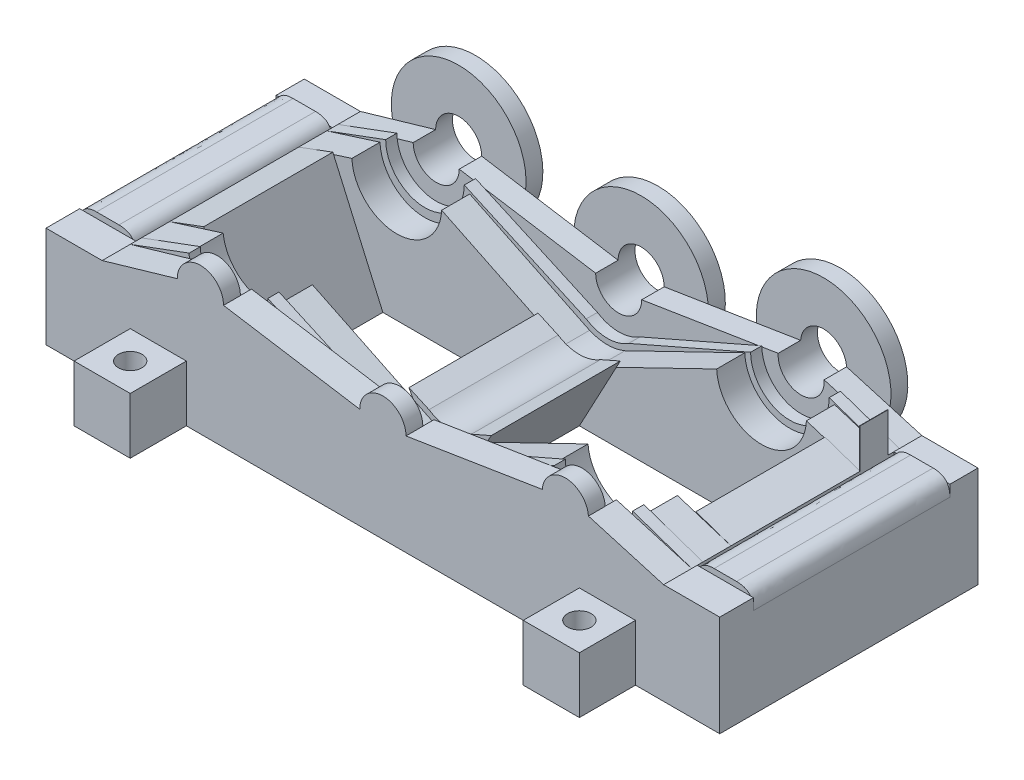
SolidWorks part; units mm, degrees
ref_plane "Спереди" through (0, 0, 0) normal (0, 0, 1) x (1, 0, 0)
ref_plane "Сверху" through (0, 0, 0) normal (0, 1, 0) x (1, 0, 0)
ref_plane "Справа" through (0, 0, 0) normal (1, 0, 0) x (0, 0, -1)
sketch "Эскиз1" plane through (0, 0, 0) normal (0, 1, 0) x (1, 0, 0)
  line L4 (-60, 16) -> (-60, 11)
  line L5 (-60, -30) -> (-60, -24)
  line L6 (-60, -24) -> (-60, 11)
  line L7 (60, 16) -> (60, 11)
  line L8 (60, 11) -> (60, -24)
  line L9 (60, -24) -> (60, -30)
  line L10 (-60, 11) -> (-50, 11)
  line L11 (-60, -24) -> (-50, -24)
  line L12 (-60, 16) -> (-55, 16)
  line L13 (-55, 16) -> (55, 16)
  line L14 (55, 16) -> (60, 16)
  line L15 (-60, 16) -> (-60, 43)
  line L16 (-60, 43) -> (-60, 48)
  line L17 (-60, -30) -> (-45, -30)
  line L18 (-45, -30) -> (-35, -30)
  line L19 (-35, -30) -> (35, -30)
  line L20 (35, -30) -> (45, -30)
  line L21 (45, -30) -> (60, -30)
  line L22 (-60, -45) -> (-60, -30)
  line L23 (-60, -45) -> (-45, -45)
  line L24 (-45, -40) -> (-35, -40)
  line L25 (-35, -40) -> (-35, -30)
  line L26 (-45, -30) -> (-45, -40)
  line L27 (-45, -45) -> (-45, -40)
  line L28 (60, -30) -> (60, -45)
  line L29 (35, -40) -> (45, -40)
  line L30 (45, -45) -> (45, -40)
  line L31 (45, -40) -> (45, -30)
  line L32 (35, -30) -> (35, -40)
  line L33 (45, -45) -> (60, -45)
  line L34 (-50, -24) -> (50, -24)
  line L35 (50, -24) -> (60, -24)
  line L36 (-50, 11) -> (50, 11)
  line L37 (50, 11) -> (60, 11)
  line L38 (-50, -24) -> (-50, 11)
  line L39 (50, -24) -> (50, 11)
  line L40 (60, 16) -> (60, 43)
  line L41 (60, 43) -> (60, 48)
  line L42 (55, 16) -> (55, 43)
  line L43 (55, 43) -> (-55, 43)
  line L44 (-55, 43) -> (-55, 16)
  line L45 (-60, 48) -> (-45, 48)
  line L46 (-45, 48) -> (-35, 48)
  line L47 (60, 48) -> (45, 48)
  line L48 (45, 48) -> (35, 48)
  line L49 (35, 48) -> (-35, 48)
  line L50 (-60, 63) -> (-60, 48)
  line L51 (-60, 63) -> (-45, 63)
  line L52 (-45, 58) -> (-45, 48)
  line L53 (-45, 58) -> (-45, 63)
  line L54 (-45, 58) -> (-35, 58)
  line L55 (-35, 58) -> (-35, 48)
  line L56 (60, 48) -> (60, 63)
  line L57 (60, 63) -> (45, 63)
  line L58 (45, 63) -> (45, 58)
  line L59 (45, 58) -> (45, 48)
  line L60 (45, 58) -> (35, 58)
  line L61 (35, 58) -> (35, 48)
  circle A0 centre (-40, -35) radius 2.1
  circle A1 centre (-52.5, -37.5) radius 3
  circle A2 centre (40, -35) radius 2.1
  circle A3 centre (52.5, -37.5) radius 3
  circle A4 centre (-52.5, 55.5) radius 3
  circle A5 centre (-40, 53) radius 2.1
  circle A6 centre (40, 53) radius 2.1
  circle A7 centre (52.5, 55.5) radius 3
extrude "Бобышка-Вытянуть4" add sketch "Эскиз1<5>" along normal blind 10 contours L18 L26 L24 L25 A0 | L20 L32 L29 L31 A2 region at (-40, 0, 30.1414) region at (40, 0, 30.1414)
sketch "Эскиз1<5>" plane through (0, 0, 0) normal (0, 1, 0) x (1, 0, 0) same geometry as "Эскиз1"
extrude "Бобышка-Вытянуть5" add sketch "Эскиз1<6>" along normal blind 35 contours L48 L49 L46 L45 L16 L15 L12 L44 L43 L42 L14 L40 L41 L47 | L55 L54 L52 L46 A5 | L60 L61 L48 L59 A6 region at (-58.7581, 0, -29.5) region at (-44.8586, 0, -53) region at (35.1414, 0, -53)
sketch "Эскиз1<6>" plane through (0, 0, 0) normal (0, 1, 0) x (1, 0, 0) same geometry as "Эскиз1"
extrude "Бобышка-Вытянуть7" add sketch "Эскиз1" along normal blind 19 contours L39 L35 L8 L37 | L11 L38 L10 L6 region at (-55, 0, 6.5) region at (55, 0, 6.5)
fillet "Скругление8" radius 3 2 edges at (-60, 19, 6.5) (-50, 19, 6.5) conic rho 0.5
fillet "Скругление9" radius 3 2 edges at (50, 19, 6.5) (60, 19, 6.5) conic rho 0.5
extrude "Бобышка-Вытянуть8" add sketch "Эскиз1<9>" along normal blind 18 contours L36 L37 L7 L14 L13 L12 L4 L10 | L35 L34 L11 L5 L17 L18 L19 L20 L21 L9 region at (0, 0, -13.5) region at (0, 0, 27)
sketch "Эскиз1<9>" plane through (0, 0, 0) normal (0, 1, 0) x (1, 0, 0) same geometry as "Эскиз1"
ref_plane "Плоскость1" through (-60, 0, 0) normal (-1, 0, 0) x (0, 0, 1)
sketch "Эскиз2" plane through (-60, 0, 0) normal (-1, 0, 0) x (0, 0, 1)
  line L0 (-58, 0) -> (-21, 0)
  line L7 (30, 0) -> (-48, 0) construction
  line L8 (-21, 0) -> (-21, 30)
  line L9 (-21, 30) -> (-58, 30)
  line L10 (-58, 30) -> (-58, 0)
extrude "Вырез-Вытянуть2" cut sketch "Эскиз2" against normal through all
ref_plane "Плоскость2" through (0, 0, 30) normal (0, 0, 1) x (1, 0, 0)
sketch "Эскиз3" plane through (0, 0, 30) normal (0, 0, 1) x (1, 0, 0)
  line L0 (-4.1, 18) -> (4.1, 18)
  arc A1 (-4.1, 18) -> (4.1, 18) centre (0, 18) ccw
extrude "Вырез-Вытянуть3" cut sketch "Эскиз3" against normal through all both and the other way through all
ref_plane "Плоскость3" through (0, 0, -16) normal (0, 0, -1) x (-1, 0, 0)
sketch "Эскиз6" plane through (0, 0, -16) normal (0, 0, -1) x (-1, 0, 0)
  line L13 (31.2351, 18) -> (33.7649, 18)
  line L18 (-28.4105, 21.9) -> (-4.1, 18)
  line L20 (-50, 18) -> (-34.4499, 18)
  line L22 (28.4, 21.9) -> (36.6, 21.9)
  line L23 (36.6, 21.9) -> (50, 18)
  line L24 (28.4, 21.9) -> (4.1, 18)
  line L25 (4.1, 18) -> (31.2351, 18)
  line L26 (50, 18) -> (33.7649, 18)
  line L28 (-30.5501, 18) -> (-4.1, 18)
  line L29 (-36.5895, 21.9) -> (-50, 18)
  line L31 (-34.4499, 18) -> (-30.5501, 18)
  arc A6 (28.4, 21.9) -> (31.2351, 18) centre (32.5, 21.9) ccw
  arc A12 (31.2351, 18) -> (33.7649, 18) centre (32.5, 21.9) ccw
  arc A13 (33.7649, 18) -> (36.6, 21.9) centre (32.5, 21.9) ccw
  arc A16 (-30.5501, 18) -> (-28.4105, 21.9) centre (-32.5, 21.6066) ccw
  arc A20 (-36.5895, 21.9) -> (-34.4499, 18) centre (-32.5, 21.6066) ccw
  arc A21 (-34.4499, 18) -> (-30.5501, 18) centre (-32.5, 21.6066) ccw
ref_plane "Плоскость4" through (0, 0, 30) normal (0, 0, 1) x (1, 0, 0)
sketch "Эскиз9" plane through (-60, 0, 0) normal (-1, 0, 0) x (0, 0, 1)
  line L0 (-58, 34.892) -> (-58, 35)
  line L1 (-58, 35) -> (-58, 30) construction
  line L2 (-58, 34.9) -> (-58, 43.9) construction
  line L3 (-58, 35) -> (-16, 35)
  line L4 (-16, 35) -> (-16, 34.9)
  line L5 (-16, 35) -> (-16, 18) construction
  line L6 (-16, 34.9) -> (-16, 44.9) construction
  line L7 (-16, 34.9) -> (-58, 34.892)
extrude "Вырез-Вытянуть6" cut sketch "Эскиз9" against normal through all both and the other way through all
ref_plane "Плоскость5" through (0, 0, 24) normal (0, 0, -1) x (-1, 0, 0)
ref_plane "Плоскость6" through (0, 0, -16) normal (0, 0, -1) x (-1, 0, 0)
sketch "Эскиз13" plane through (0, 0, -16) normal (0, 0, -1) x (-1, 0, 0)
  circle A0 centre (0, 18) radius 4.1
  circle A1 centre (0, 18) radius 12
  circle A2 centre (-32.5, 21.6066) radius 4.1
  circle A3 centre (-32.5, 21.6066) radius 12
  circle A4 centre (32.5, 21.9) radius 4.1
  circle A5 centre (32.5, 21.9) radius 12
extrude "Бобышка-Вытянуть20" add sketch "Эскиз13" along normal blind 3
ref_plane "Плоскость7" through (0, 0, 0) normal (0, -1, 0) x (-1, 0, 0)
sketch "Эскиз14" plane through (0, 0, 0) normal (0, -1, 0) x (-1, 0, 0)
  line L0 (-55, 16) -> (-55, 43)
  line L1 (-55, 43) -> (55, 43)
  line L2 (-55, 43) -> (55, 43) construction
  line L3 (55, 43) -> (55, 16)
  line L4 (55, 16) -> (60, 16)
  line L5 (60, -30) -> (60, 21) construction
  line L6 (9.9, 16) -> (-9.9, 16) construction
  line L7 (60, 16) -> (60, 63)
  line L8 (60, 63) -> (-60, 63)
  line L9 (-45, 63) -> (-60, 63) construction
  line L10 (-60, 63) -> (-60, 16)
  line L11 (-60, 21) -> (-60, -30) construction
  line L12 (-60, 16) -> (-55, 16)
  line L13 (-60, 63) -> (-60, 16) construction
extrude "Вырез-Вытянуть9" cut sketch "Эскиз14" against normal blind 40
extrude "Бобышка-Вытянуть21" add sketch "Эскиз6" against normal blind 5 contours A20 L29 L20 | A16 L28 L18 | A6 L24 L25 | A13 L26 L23 region at (-20.8202, 19.2763, -16) region at (-40.5357, 19.259, -16) region at (40.6671, 19.2635, -16) region at (20.6921, 19.2791, -16)
extrude "Вырез-Вытянуть10" cut sketch "Эскиз6<10>" against normal blind 5 contours L31 A21 | L13 A12 region at (-32.5, 17.9198, -16) region at (32.5, 17.8016, -16)
sketch "Эскиз6<10>" plane through (0, 0, -16) normal (0, 0, -1) x (-1, 0, 0) same geometry as "Эскиз6"
sketch "Эскиз15" plane through (0, 0, 30) normal (0, 0, 1) x (1, 0, 0)
  line L0 (-33.7649, 18) -> (-31.2351, 18)
  line L1 (-60, 18) -> (-4.1, 18) construction
  line L2 (-31.2351, 18) -> (-4.1, 18)
  line L3 (-4.1, 18) -> (-28.4, 21.9)
  line L5 (-33.7649, 18) -> (-50, 18)
  line L6 (-36.6, 21.9) -> (-50, 18) construction
  line L7 (-50, 18) -> (-36.6, 21.9)
  line L8 (30.5255, 18) -> (34.4618, 18)
  line L9 (4.1, 18) -> (60, 18) construction
  line L10 (34.4618, 18) -> (50, 18)
  line L11 (36.5895, 21.9) -> (50, 18) construction
  line L15 (4.1, 18) -> (30.5255, 18)
  line L16 (36.5895, 21.9) -> (50, 18)
  line L17 (4.1, 18) -> (28.4105, 21.9)
  arc A2 (-36.6, 21.9) -> (-33.7649, 18) centre (-32.5, 21.9) ccw
  arc A3 (-31.2351, 18) -> (-28.4, 21.9) centre (-32.5, 21.9) ccw
  arc A4 (-31.2351, 18) -> (-33.7649, 18) centre (-32.5, 21.9) cw
  arc A6 (30.5255, 18) -> (34.4618, 18) centre (32.4936, 21.5995) ccw
  arc A8 (28.4105, 21.9) -> (30.5255, 18) centre (32.4869, 21.5871) ccw
  arc A9 (34.4618, 18) -> (36.5895, 21.9) centre (32.49, 21.6061) ccw
extrude "Бобышка-Вытянуть22" add sketch "Эскиз15" against normal blind 6 contours A2 L7 L5 | A3 L2 L3 | A8 L17 L15 | A9 L10 L16 region at (-20.8202, 19.2763, 30) region at (-40.5357, 19.259, 30) region at (40.6688, 19.2637, 30) region at (20.6854, 19.2792, 30)
extrude "Вырез-Вытянуть11" cut sketch "Эскиз15<4>" against normal blind 6 contours A4 L0 | L8 A6 region at (-32.5, 17.9198, 30) region at (32.4936, 17.7977, 30)
sketch "Эскиз15<4>" plane through (0, 0, 30) normal (0, 0, 1) x (1, 0, 0) same geometry as "Эскиз15"
sketch "Эскиз16" plane through (0, 0, 30) normal (0, 0, 1) x (1, 0, 0)
  circle A0 centre (-32.5, 21.9) radius 4.12
  circle A1 centre (0, 18) radius 4.12
  circle A2 centre (32.5, 21.6066) radius 4.12
extrude "Бобышка-Вытянуть45" add sketch "Эскиз16" against normal blind 3
sketch "Эскиз18" plane through (0, 0, 24) normal (0, 0, -1) x (-1, 0, 0)
  line L0 (-50, 18) -> (-50, 0)
  line L1 (-55.3642, 0) -> (55.3642, 0) construction
  line L2 (50, 18) -> (50, 0)
  line L3 (50, 16) -> (50, 0) construction
  line L4 (50, 0) -> (-50, 0)
  line L5 (50, 18) -> (38.9635, 21.2121)
  line L6 (36.6, 21.9) -> (50, 18) construction
  line L7 (26.0113, 21.5166) -> (6.4887, 18.3834)
  line L8 (28.4, 21.9) -> (4.1, 18) construction
  line L9 (-26.0006, 21.5166) -> (-6.4887, 18.3832)
  line L10 (-28.4105, 21.9) -> (-4.1, 18) construction
  line L11 (-50, 18) -> (-38.988, 21.2121)
  arc A3 (-38.988, 21.2121) -> (-26.0006, 21.5166) centre (-32.5, 21.6066) ccw
  arc A4 (6.4887, 18.3834) -> (-6.4887, 18.3832) centre (0, 18) cw
  arc A5 (38.9635, 21.2121) -> (26.0113, 21.5166) centre (32.5, 21.9) cw
extrude "Вырез-Вытянуть12" cut sketch "Эскиз18" along normal blind 36 and the other way blind 1
sketch "Эскиз19" plane through (0, 0, 0) normal (0, -1, 0) x (-1, 0, 0)
  line L0 (-50, -25) -> (-50, -23)
  line L2 (-50, -25) -> (-50, 12) construction
  line L3 (-50, -23) -> (-50, -18)
  line L4 (-50, -18) -> (-50, 5)
  line L5 (-50, 5) -> (-50, 10)
  line L6 (-50, 10) -> (-50, 12)
  line L7 (-50, 12) -> (50, 12)
  line L8 (-50, 10) -> (50, 10)
  line L9 (50, -25) -> (50, 12) construction
  line L10 (-50, 5) -> (50, 5)
  line L11 (-50, -18) -> (50, -18)
  line L12 (-50, -23) -> (50, -23)
  line L13 (-50, -25) -> (50, -25)
  line L14 (50, -25) -> (50, -23)
  line L15 (50, -18) -> (50, 5)
  line L16 (50, 10) -> (50, 12)
  line L17 (50, -18) -> (50, -23)
  line L18 (50, 10) -> (50, 5)
extrude "Бобышка-Вытянуть46" add sketch "Эскиз19" against normal blind 25 contours L18 L8 L5 L10 | L17 L11 L3 L12 region at (0, 0, 20.5) region at (0, 0, -7.5)
ref_plane "Плоскость9" through (0, 0, 23) normal (0, 0, 1) x (1, 0, 0)
sketch "Эскиз21" plane through (0, 0, 23) normal (0, 0, 1) x (1, 0, 0)
  line L0 (-24.5516, 20.9931) -> (-3.2499, 10.6579)
  line L2 (3.1623, 10.6198) -> (24.5344, 20.9749)
  line L3 (40.4673, 20.9971) -> (50, 18)
  line L4 (50, 18) -> (50, 32.9969)
  line L5 (-40.4505, 21.0111) -> (-50, 18)
  line L6 (-50, 18) -> (-50, 32.9969)
  line L7 (-50, 32.9969) -> (50, 32.9969)
  circle A0 centre (0, 18) radius 8.0292
  circle A1 centre (-32.5, 21.9) radius 8
  circle A2 centre (32.5, 21.6066) radius 7.9906
extrude "Вырез-Вытянуть15" cut sketch "Эскиз21" against normal blind 5 contours A2 L3 L4 L7 L6 L5 A1 L0 A0 L2 | L0 A0 L2 | A1 | A2 region at (0.1494, 26.3073, 23) region at (-32.5, 21.9, 23) region at (0, 18.0002, 23) region at (32.5, 21.6066, 23)
ref_plane "Плоскость10" through (0, 0, -5) normal (0, 0, 1) x (1, 0, 0)
sketch "Эскиз22" plane through (0, 0, -5) normal (0, 0, 1) x (1, 0, 0)
  line L0 (-24.5312, 21) -> (-3.182, 10.6466)
  line L2 (3.1197, 10.6466) -> (24.4532, 21)
  line L3 (40.4376, 21) -> (49.9376, 18)
  line L4 (49.9376, 18) -> (49.9376, 32.9969)
  line L5 (-40.5156, 21) -> (-50, 18)
  line L6 (-50, 18) -> (-50, 32.9969)
  line L7 (-50, 32.9969) -> (49.9376, 32.9969)
  circle A0 centre (-0.0312, 18) radius 8
  circle A1 centre (-32.5234, 21.353) radius 8
  circle A2 centre (32.4454, 21.353) radius 8
extrude "Вырез-Вытянуть16" cut sketch "Эскиз22" against normal blind 5 contours A2 L3 L4 L7 L6 L5 A1 L0 A0 L2 | A2 | L0 A0 L2 | A1 region at (-0.03, 26.3324, -5) region at (-32.5234, 21.353, -5) region at (-0.0312, 18.0003, -5) region at (32.4454, 21.353, -5)
extrude "Бобышка-Вытянуть47" add sketch "Эскиз19<4>" against normal blind 25 contours L8 L16 L7 L6 region at (0, 0, -11)
sketch "Эскиз19<4>" plane through (0, 0, 0) normal (0, -1, 0) x (-1, 0, 0) same geometry as "Эскиз19"
ref_plane "Плоскость11" through (0, 0, -10) normal (0, 0, 1) x (1, 0, 0)
sketch "Эскиз23" plane through (0, 0, -10) normal (0, 0, 1) x (1, 0, 0)
  line L0 (-25.5, 21.9) -> (-3.7867, 12.1127)
  line L2 (3.7867, 12.1127) -> (25.5, 21.6066)
  line L3 (39.5, 21.6066) -> (50, 18)
  line L4 (50, 18) -> (50, 33)
  line L5 (-39.5, 21.9) -> (-50, 18)
  line L6 (-50, 18) -> (-50, 33)
  line L7 (-50, 33) -> (50, 33)
  circle A3 centre (0, 18) radius 7
  circle A4 centre (-32.5, 21.9) radius 7
  circle A5 centre (32.5, 21.6066) radius 7
extrude "Вырез-Вытянуть18" cut sketch "Эскиз23" against normal blind 2 contours A5 L3 L4 L7 L6 L5 A4 L0 A3 L2 | A4 | A3 | A5 L0 region at (0.2254, 26.3963, -10) region at (-32.5, 21.9, -10) region at (0, 18, -10) region at (32.5, 21.6066, -10)
extrude "Бобышка-Вытянуть49" add sketch "Эскиз19<6>" against normal blind 25 contours L11 L15 L10 L4 | L13 L14 L12 L0 region at (0, 0, 24) region at (0, 0, 6.5)
sketch "Эскиз19<6>" plane through (0, 0, 0) normal (0, -1, 0) x (-1, 0, 0) same geometry as "Эскиз19"
ref_plane "Плоскость12" through (0, 0, 18) normal (0, 0, 1) x (1, 0, 0)
ref_plane "Плоскость13" through (0, 0, 25) normal (0, 0, 1) x (1, 0, 0)
sketch "Эскиз24" plane through (0, 0, 18) normal (0, 0, 1) x (1, 0, 0)
  line L0 (-25.5, 21.9) -> (-3.7867, 12.1127)
  line L2 (3.7867, 12.1127) -> (25.5, 21.6066)
  line L3 (39.5, 21.6066) -> (50, 18)
  line L4 (50, 18) -> (50, 33)
  line L5 (-39.5, 21.9) -> (-50, 18)
  line L6 (-50, 18) -> (-50, 33)
  line L7 (-50, 33) -> (50, 33)
  circle A3 centre (0, 18) radius 7
  circle A4 centre (-32.5, 21.9) radius 7
  circle A5 centre (32.5, 21.6066) radius 7
extrude "Вырез-Вытянуть20" cut sketch "Эскиз24" against normal blind 23 contours A4 | A5 L3 L4 L7 L6 L5 A4 L0 A3 L2 | A3 | A5 L0 region at (0.2254, 26.3963, 18) region at (-32.5, 21.9, 18) region at (0, 18, 18) region at (32.5, 21.6066, 18)
sketch "Эскиз26" plane through (0, 0, 25) normal (0, 0, 1) x (1, 0, 0)
  line L0 (-25.5, 21.9) -> (-3.7867, 12.1127)
  line L2 (3.7867, 12.1127) -> (25.5, 21.6066)
  line L3 (39.5, 21.6066) -> (50, 18)
  line L4 (50, 18) -> (50, 33)
  line L5 (-39.5, 21.9) -> (-50, 18)
  line L6 (-50, 18) -> (-50, 33)
  line L7 (-50, 33) -> (50, 33)
  circle A3 centre (0, 18) radius 7
  circle A4 centre (-32.5, 21.9) radius 7
  circle A5 centre (32.5, 21.6066) radius 7
extrude "Вырез-Вытянуть21" cut sketch "Эскиз26" against normal blind 2 contours A5 L3 L4 L7 L6 L5 A4 L0 A3 L2 | A4 | A3 | A5 region at (0.2254, 26.3963, 25) region at (-32.5, 21.9, 25) region at (0, 18, 25) region at (32.5, 21.6066, 25)
sketch "Эскиз27" plane through (0, 0, 18) normal (0, 0, 1) x (1, 0, 0)
  line L0 (-45.8652, 24.703) -> (-35, 0)
  line L1 (-28.4, 21.9) -> (-4.1, 18) construction
  line L2 (-35, 0) -> (0, 0)
  line L3 (0, 0) -> (-10.1738, 18.9748)
  line L6 (28.4105, 21.9) -> (4.1, 18) construction
  line L7 (10.1388, 18.9688) -> (0, 0)
  line L8 (-10.1738, 18.9748) -> (-22.6307, 23.4755)
  line L9 (45.7239, 24.6775) -> (35, 0)
  line L10 (35, 0) -> (0, 0)
  line L11 (-22.6307, 23.4755) -> (-45.8652, 24.703)
  line L13 (21.1357, 23.4755) -> (10.1388, 18.9688)
  line L14 (21.1357, 23.4755) -> (45.7239, 24.6775)
extrude "Вырез-Вытянуть22" cut sketch "Эскиз27" against normal blind 23 contours L3 L0 L2 | L10 L9 L7 region at (-23.6569, 11.5266, 18) region at (23.5912, 11.5727, 18)
